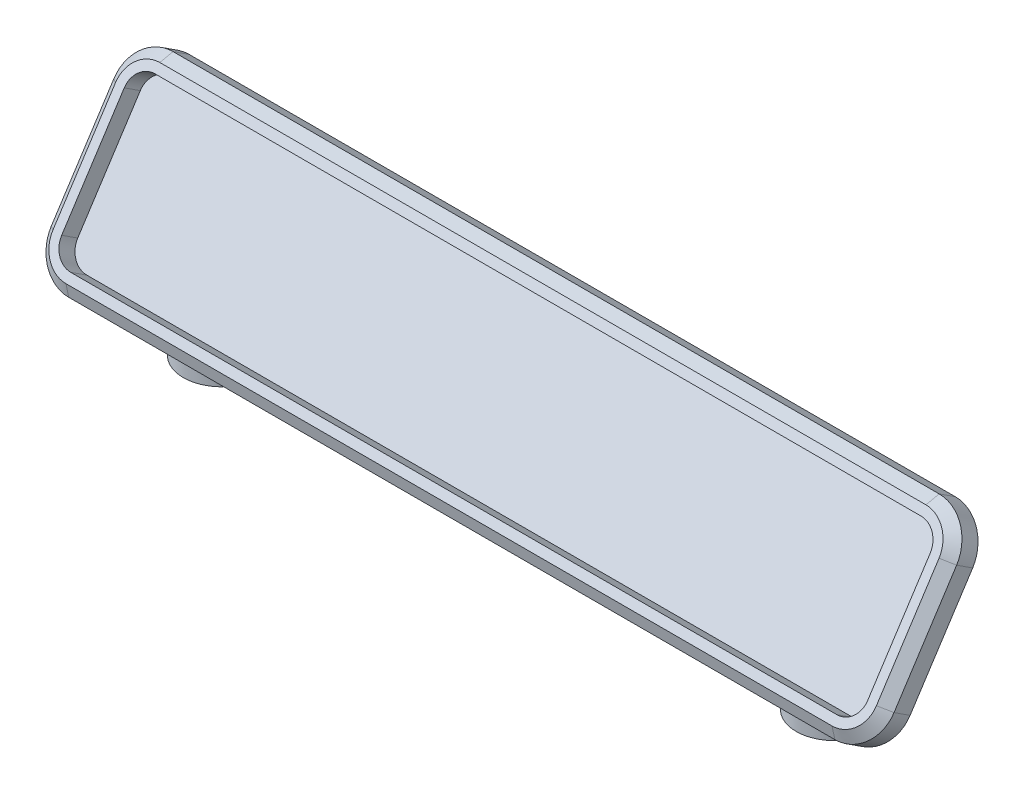
SolidWorks part; units mm, degrees
note: '?' marks a value the reader was unsure of.
ref_plane "Front Plane" through (0, 0, 0) normal (0, 0, 1) x (1, 0, 0)
ref_plane "Top Plane" through (0, 0, 0) normal (0, 1, 0) x (1, 0, 0)
ref_plane "Right Plane" through (0, 0, 0) normal (1, 0, 0) x (0, 0, -1)
sketch "Sketch2" plane through (0, 0, 0) normal (0, 1, 0) x (1, 0, 0)
  line L0 (50.8, 0) -> (-50.8, 0) construction
  circle A0 centre (-50.8, 0) radius 6.35
  circle A1 centre (50.8, 0) radius 6.35
  point P8 (0, 0)
  dimension "D2" = 12.7
  dimension "D1" = 101.6
extrude "Boss-Extrude1" add sketch "Sketch2" along normal blind 19.05
ref_plane "Plane1" through (0, 19.05, 0) normal (0, 1, 0) x (1, 0, 0)
ref_axis "Axis1" through (88.99, 19.05, 0) along (-1, 0, 0)?
ref_plane "Plane2" through (0, 5.6508, 8.7015) normal (0, 0.5446, 0.8387) x (-1, 0, 0)
sketch "Sketch3" plane through (0, 5.6508, 8.7015) normal (0, 0.5446, 0.8387) x (-1, 0, 0)
  line L0 (-50.8, -15.9767) -> (50.8, -15.9767)
  line L2 (-63.5, -31.8517) -> (63.5, -31.8517)
  line L3 (-69.85, -25.5017) -> (-69.85, -6.4517)
  line L4 (-63.5, -0.1017) -> (63.5, -0.1017)
  line L5 (69.85, -25.5017) -> (69.85, -6.4517)
  line L6 (-69.85, -31.8517) -> (69.85, -0.1017) construction
  line L7 (-69.85, -0.1017) -> (69.85, -31.8517) construction
  arc A0 (-63.5, -31.8517) -> (-69.85, -25.5017) centre (-63.5, -25.5017) cw
  arc A1 (63.5, -31.8517) -> (69.85, -25.5017) centre (63.5, -25.5017) ccw
  arc A2 (63.5, -0.1017) -> (69.85, -6.4517) centre (63.5, -6.4517) cw
  arc A3 (-69.85, -6.4517) -> (-63.5, -0.1017) centre (-63.5, -6.4517) cw
  ellipse E0 centre (50.8, -15.9767) end of major axis (44.45, -15.9767) minor radius 3.4585 construction
  ellipse E1 centre (-50.8, -15.9767) end of major axis (-57.15, -15.9767) minor radius 3.4585 construction
  ellipse E2 centre (50.8, -15.9767) end of major axis (44.45, -15.9767) minor radius 3.4585 construction
  ellipse E3 centre (-50.8, -15.9767) end of major axis (-57.15, -15.9767) minor radius 3.4585 construction
  point P22 (0, -15.9767)
  dimension "D3" = 6.35
  dimension "D1" = 139.7
  dimension "D2" = 31.75
extrude "Boss-Extrude2" add sketch "Sketch3" along normal blind 6.35
sketch "Sketch8" plane through (0, 19.05, 0) normal (0, 1, 0) x (1, 0, 0)
  line L0 (44.45, 0) -> (57.15, 0) construction
  line L1 (-57.15, 0) -> (-44.45, 0) construction
  line L2 (44.45, 0) -> (57.15, 0)
  line L3 (-57.15, 0) -> (-44.45, 0)
  arc A0 (57.15, 0) -> (44.45, 0) centre (50.8, 0) ccw construction
  arc A1 (-44.45, 0) -> (-57.15, 0) centre (-50.8, 0) ccw construction
  arc A2 (57.15, 0) -> (44.45, 0) centre (50.8, 0) ccw
  arc A3 (-44.45, 0) -> (-57.15, 0) centre (-50.8, 0) ccw
extrude "Boss-Extrude3" add sketch "Sketch8" along normal up to next contours L2 A2 | A3 L3
sketch "Sketch9" plane through (0, 9.1093, 14.0271) normal (0, 0.5446, 0.8387) x (1, 0, 0)
  line L8 (63.5, 28.8037) -> (-63.5, 28.8037)
  line L9 (-66.802, 25.5017) -> (-66.802, 6.4517)
  line L10 (-63.5, 3.1497) -> (63.5, 3.1497)
  line L11 (66.802, 6.4517) -> (66.802, 25.5017)
  line L12 (63.5, 28.8037) -> (-63.5, 28.8037)
  line L13 (-66.802, 25.5017) -> (-66.802, 6.4517)
  line L14 (-63.5, 3.1497) -> (63.5, 3.1497)
  line L15 (66.802, 6.4517) -> (66.802, 25.5017)
  arc A8 (63.5, 3.1497) -> (66.802, 6.4517) centre (63.5, 6.4517) ccw
  arc A9 (63.5, 3.1497) -> (66.802, 6.4517) centre (63.5, 6.4517) ccw
  arc A10 (66.802, 25.5017) -> (63.5, 28.8037) centre (63.5, 25.5017) ccw
  arc A11 (66.802, 25.5017) -> (63.5, 28.8037) centre (63.5, 25.5017) ccw
  arc A12 (-63.5, 28.8037) -> (-66.802, 25.5017) centre (-63.5, 25.5017) ccw
  arc A13 (-63.5, 28.8037) -> (-66.802, 25.5017) centre (-63.5, 25.5017) ccw
  arc A14 (-66.802, 6.4517) -> (-63.5, 3.1497) centre (-63.5, 6.4517) ccw
  arc A15 (-66.802, 6.4517) -> (-63.5, 3.1497) centre (-63.5, 6.4517) ccw
  dimension "D1" = 3.048
extrude "Cut-Extrude1" cut sketch "Sketch9" against normal blind 3.175
chamfer "Chamfer2" distance 1.5875 angle 45 16 edges at (-69.85, 19.05, 0) (0, 32.3639, -8.6461) (69.85, 19.05, 0) (0, 5.7361, 8.6461) (0, 9.1946, 13.9717) (-69.85, 22.5085, 5.3256) (69.85, 22.5085, 5.3256) (0, 35.8224, -3.3206) (67.9901, 30.8041, -7.6332) (-67.9901, 30.8041, -7.6332) (67.9901, 7.2959, 7.6332) (-67.9901, 7.2959, 7.6332) (67.9901, 10.7544, 12.9587) (-67.9901, 10.7544, 12.9587) (67.9901, 34.2625, -2.3076) (-67.9901, 34.2625, -2.3076)
hole_wizard "Hole1" positions "3DSketch1" profile "Sketch10" legacy
sketch3d "3DSketch1"
  line L0 (-50.8, 28.8281, 0) -> (-50.8, 0, 0) construction
  line L1 (50.8, 28.8281, 0) -> (50.8, 0, 0) construction
  point P0 (-50.8, 0, 0)
  point P4 (50.8, 0, 0)
sketch "Sketch10" plane through (-50.8, 0, 0) normal (1, 0, 0) x (0, 0, -1)
  line L0 (0, 0) -> (0, 10.16)
  line L1 (0, 10.16) -> (2.8575, 10.16)
  line L2 (2.8575, 10.16) -> (2.8575, 0.6858)
  line L3 (2.8575, 0.6858) -> (3.4925, 0.6858)
  line L4 (3.4925, 0.6858) -> (3.4925, 0)
  line L5 (3.4925, 0) -> (0, 0)
  line L6 (0, 110) -> (0, -10) construction
  dimension "Diameter" = 5.715
  dimension "Depth" = 10.16
  dimension "C-Bore Diameter" = 6.985
  dimension "C-Bore Depth" = 0.6858
